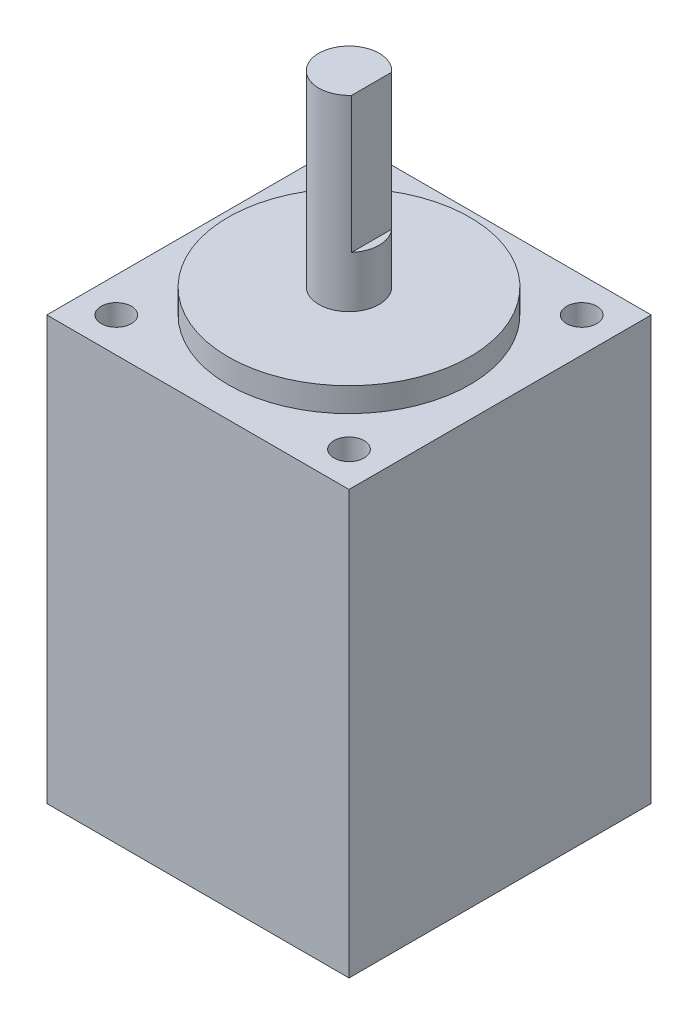
SolidWorks part; units mm, degrees
ref_plane "前视基准面" through (0, 0, 0) normal (0, 0, 1) x (1, 0, 0)
ref_plane "上视基准面" through (0, 0, 0) normal (0, 1, 0) x (1, 0, 0)
ref_plane "右视基准面" through (0, 0, 0) normal (1, 0, 0) x (0, 0, -1)
sketch "草图1" plane through (0, 0, 0) normal (0, 1, 0) x (1, 0, 0)
  line L0 (0, 0) -> (20, 0)
  line L1 (20, 0) -> (20, 20)
  line L2 (0, 0) -> (0, 20)
  line L3 (0, 20) -> (20, 20)
  circle A0 centre (17.7, 2.3) radius 1
  circle A1 centre (17.7, 17.7) radius 1
  circle A2 centre (2.3, 17.7) radius 1
  circle A3 centre (2.3, 2.3) radius 1
extrude "凸台-拉伸1" add sketch "草图1" along normal blind 28
sketch "草图2" plane through (0, 28, 0) normal (0, 1, 0) x (1, 0, 0)
  line L0 (20, 10) -> (0, 10)
  line L1 (20, 0) -> (20, 20) construction
  line L2 (0, 20) -> (0, 0) construction
  circle A0 centre (10, 10) radius 8
extrude "凸台-拉伸2" add sketch "草图2" along normal blind 1.6 contours L0 A0 | L0 A0 region at (10, 28, -6.6047) region at (10, 28, -13.3953)
sketch "草图3" plane through (0, 29.6, 0) normal (0, 1, 0) x (1, 0, 0)
  circle A0 centre (10, 10) radius 2
extrude "凸台-拉伸3" add sketch "草图3" along normal blind 12.4
sketch "草图4" plane through (0, 42, 0) normal (0, 1, 0) x (1, 0, 0)
  line L0 (8, 10) -> (11.5011, 10)
  line L1 (11.5011, 10) -> (11.5011, 8.6784)
  line L2 (11.5011, 8.6784) -> (11.5011, 11.3216)
  circle A0 centre (10, 10) radius 2 construction
  circle A1 centre (10, 10) radius 2 construction
  circle A2 centre (10, 10) radius 2
  circle M3 centre (10, 10) radius 2
extrude "切除-拉伸4" cut sketch "草图4" against normal blind 9 contours L2 L1 M3 region at (11.703, 42, -10)
